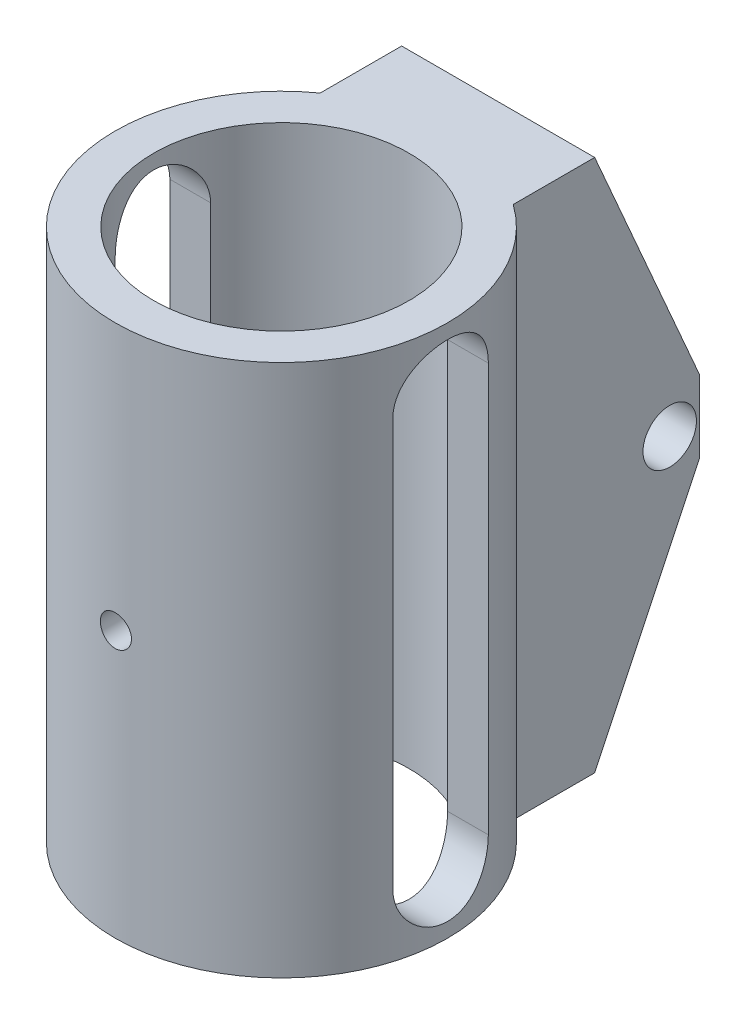
SolidWorks part; units mm, degrees
ref_plane "Front Plane" through (0, 0, 0) normal (0, 0, 1) x (1, 0, 0)
ref_plane "Top Plane" through (0, 0, 0) normal (0, 1, 0) x (1, 0, 0)
ref_plane "Right Plane" through (0, 0, 0) normal (1, 0, 0) x (0, 0, -1)
sketch "Sketch1" plane through (0, 0, 0) normal (0, 1, 0) x (1, 0, 0)
  circle A0 centre (0, 0) radius 8.8383
  circle A1 centre (0, 0) radius 11.5
  dimension "D1" = 17.6766
  dimension "D2" = 23
extrude "Boss-Extrude1" add sketch "Sketch1" along normal blind 36.88
ref_plane "Plane1" through (-11.5, 0, 0) normal (-1, 0, 0) x (0, 0, 1)
sketch "Sketch2" plane through (-11.5, 0, 0) normal (-1, 0, 0) x (0, 0, 1)
  line L0 (0, 32.5733) -> (0, 4.3067) construction
  line L1 (3.302, 32.5733) -> (3.302, 4.3067)
  line L2 (-3.302, 32.5733) -> (-3.302, 4.3067)
  line L3 (0, 32.5733) -> (0, 36.88) construction
  line L4 (8.8383, 36.88) -> (-8.8383, 36.88) construction
  line L5 (0, 4.3067) -> (0, 0) construction
  arc A0 (3.302, 32.5733) -> (-3.302, 32.5733) centre (0, 32.5733) ccw
  arc A1 (-3.302, 4.3067) -> (3.302, 4.3067) centre (0, 4.3067) ccw
  point P3 (0, 18.44)
  dimension "D1" = 3.302
extrude "Cut-Extrude1" cut sketch "Sketch2" against normal blind 55.88
sketch "Sketch3" plane through (0, 0, 0) normal (0, 0, 1) x (1, 0, 0)
  line L0 (0, 36.88) -> (0, 18.44) construction
  line L1 (11.5, 36.88) -> (-11.5, 36.88) construction
  circle A0 centre (0, 18.44) radius 1.0754
extrude "Cut-Extrude2" cut sketch "Sketch3" along normal through all
sketch "Sketch4" plane through (0, 0, 0) normal (0, 0, 1) x (1, 0, 0)
  line L0 (-8.8383, 0) -> (-6.6781, 0) construction
  line L5 (8.8383, 0) -> (6.6781, 0) construction
  line L6 (8.8383, 36.88) -> (6.6781, 36.88) construction
  line L7 (-8.8383, 36.88) -> (-6.6781, 36.88) construction
  line L9 (6.6781, 0) -> (-6.6781, 0)
  line L10 (6.6781, 0) -> (6.6781, 36.88)
  line L11 (6.6781, 36.88) -> (-6.6781, 36.88)
  line L12 (-6.6781, 0) -> (-6.6781, 36.88)
extrude "Boss-Extrude2" add sketch "Sketch4" along normal up to surface (5.6377 mm away) from offset 15 up to face at (11.2557, 18.44, 0) offset against normal yes
sketch "Sketch5" plane through (-6.6781, 0, 0) normal (-1, 0, 0) x (0, 0, 1)
  line L0 (-22.264, 15.2344) -> (-22.264, 20.2202)
  line L1 (-15, 36.88) -> (-22.264, 20.2202)
  line L2 (-22.264, 15.2344) -> (-15, 0)
  line L3 (-15, 17.577) -> (-20.1949, 17.577) construction
  line L4 (-15, 36.88) -> (-15, 0) construction
  circle A0 centre (-20.1949, 17.577) radius 1.85
  point P0 (-22.2657, 17.577)
  point P4 (-23.1961, 17.9759)
  point P6 (-22.2657, 17.577)
  point P11 (-23.286, 17.6423)
  point P12 (0, 0)
  point P17 (-23.381, 17.6177)
  point P18 (-23.2009, 17.577)
  line M4 (-15, 36.88) -> (-15, 0)
  dimension "D1" = 3.7
extrude "Boss-Extrude3" add sketch "Sketch5" along direction (-1, 0, 0) on the side against the normal up to surface (13.3562 mm away) contours L0 L2 L1 A0 M4 region at (-6.6781, 18.2196, -17.5206) up to face at (6.6781, 18.44, -12.1812)
